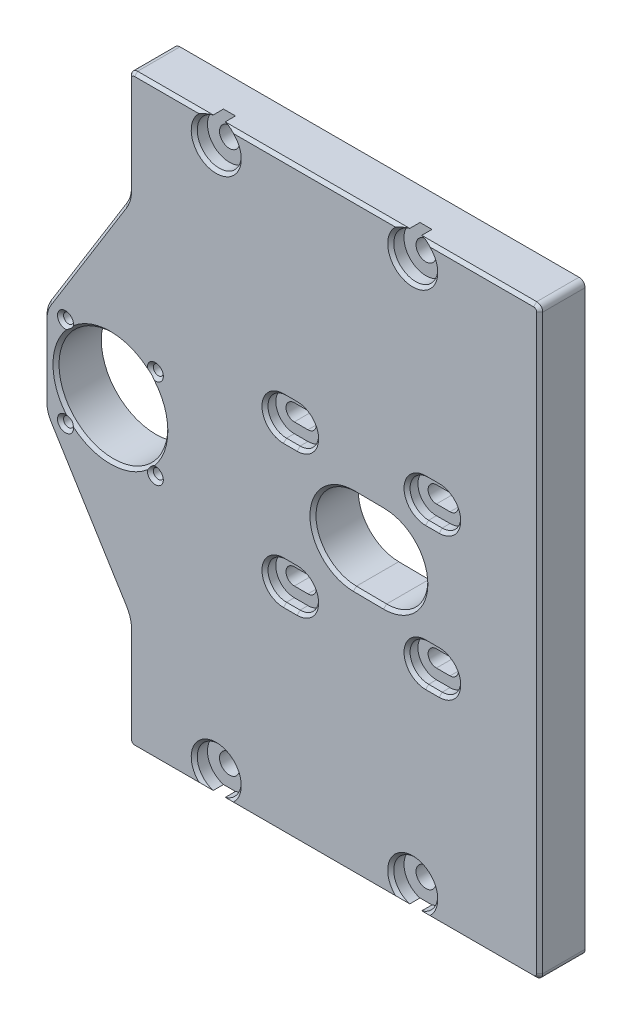
SolidWorks part; units mm, degrees
ref_plane "Front Plane" through (0, 0, 0) normal (0, 0, 1) x (1, 0, 0)
ref_plane "Top Plane" through (0, 0, 0) normal (0, 1, 0) x (1, 0, 0)
ref_plane "Right Plane" through (0, 0, 0) normal (1, 0, 0) x (0, 0, -1)
sketch "Sketch1" plane through (0, 0, 0) normal (0, 0, 1) x (1, 0, 0)
  line L24 (-148, 255) -> (-148, 190) construction
  line L31 (-148, 70) -> (-148, 10) construction
  line L32 (-148, 33.5) -> (-12, 33.5) construction
  line L36 (-12, 227) -> (-148, 227) construction
  line L37 (-148, 227) -> (-148, 190)
  line L38 (-148, 70) -> (-148, 33.5)
  line L39 (-148, 33.5) -> (-12, 33.5)
  line L43 (-12, 227) -> (-148, 227)
  line L45 (-176, 115.2267) -> (-176, 144.7733)
  line L46 (-176, 144.7733) -> (-148, 190)
  line L47 (-176, 115.2267) -> (-148, 70)
  line L51 (-12, 33.5) -> (-12, 227)
  circle A8 centre (-154, 130) radius 18
  circle A10 centre (-154, 130) radius 18
  dimension "D1" = 1
extrude "Boss-Extrude1" add sketch "Sketch1" along normal blind 15
sketch "Sketch2" plane through (0, 0, 15) normal (0, 0, 1) x (1, 0, 0)
  circle A1 centre (-139.1508, 115.1508) radius 2.25
  circle A3 centre (-168.8492, 115.1508) radius 2.25
  circle A5 centre (-168.8492, 144.8492) radius 2.25
  circle A7 centre (-139.1508, 144.8492) radius 2.25
hole_wizard "M4x0.7 Tapped Hole1" positions "Sketch3" profile "Sketch4" tap size "M4x0.7" standard "ANSI Metric"
sketch "Sketch3" plane through (0, 0, 15) normal (0, 0, 1) x (1, 0, 0)
  point P0 (-168.8492, 144.8492)
  point P3 (-139.1508, 144.8492)
  point P6 (-139.1508, 115.1508)
  point P9 (-168.8492, 115.1508)
sketch "Sketch4" plane through (-168.8492, 144.8492, 15) normal (1, 0, 0) x (0, -1, 0)
  line L0 (0, 0) -> (0, 20)
  line L1 (0, 20) -> (1.65, 19.0086)
  line L2 (1.65, 19.0086) -> (1.65, 0)
  line L5 (1.65, 0) -> (0, 0)
  line L10 (0, 20) -> (-1.65, 19.0086) construction
  line L11 (0, -6.35) -> (0, 107.95) construction
  dimension "Tap Drill Dia." = 3.3
  dimension "Tap Drill Depth" = 20
  dimension "Drill Angle" = 118
cosmetic thread "Hole Thread1" parameters "D1"=12, "D2"=4
cosmetic thread "Hole Thread2" parameters "D1"=12, "D2"=4
cosmetic thread "Hole Thread3" parameters "D1"=12, "D2"=4
cosmetic thread "Hole Thread4" parameters "D1"=12, "D2"=4
hole_wizard "CBORE for M6 Hex Head Bolt1" positions "Sketch5" profile "Sketch6" counterbore size "M6" standard "ANSI Metric"
sketch "Sketch5" plane through (0, 0, 15) normal (0, 0, 1) x (1, 0, 0)
  point P0 (-54, 220)
  point P3 (-119, 220)
  point P6 (-54, 40.5)
  point P9 (-119, 40.5)
sketch "Sketch6" plane through (-54, 220, 15) normal (1, 0, 0) x (0, -1, 0)
  line L0 (0, 0) -> (0, 29.9828)
  line L1 (0, 29.9828) -> (3.3, 28)
  line L2 (3.3, 28) -> (3.3, 4.38)
  line L3 (3.3, 4.38) -> (7.275, 4.38)
  line L4 (7.275, 4.38) -> (7.275, 0)
  line L5 (7.275, 0) -> (0, 0)
  line L10 (0, 29.9828) -> (-3.3, 28) construction
  line L11 (0, -6.35) -> (0, 107.95) construction
  dimension "Hole Dia." = 6.6
  dimension "Hole Depth" = 28
  dimension "C'Bore Dia." = 14.55
  dimension "C'Bore Depth" = 4.38
  dimension "Drill Angle" = 118
sketch "Sketch7" plane through (0, 0, 15) normal (0, 0, 1) x (1, 0, 0)
  line L0 (-73.5, 129.1439) -> (-88.5, 129.1439)
  line L1 (-89.5, 152.6439) -> (-94.5, 152.6439)
  line L2 (-42.5, 152.6439) -> (-47.5, 152.6439)
  line L3 (-42.5, 105.6439) -> (-47.5, 105.6439)
  line L4 (-89.5, 105.6439) -> (-94.5, 105.6439)
  circle A1 centre (-50, 105.6439) radius 2.85 construction
  circle A2 centre (-73.5, 129.1439) radius 13.5
  circle A3 centre (-73.5, 129.1439) radius 13.5
  circle A4 centre (-97, 105.6439) radius 2.85 construction
  circle A5 centre (-97, 152.6439) radius 2.85 construction
  circle A6 centre (-50, 152.6439) radius 2.85 construction
  circle A7 centre (-50, 105.6439) radius 2.85
  circle A8 centre (-97, 105.6439) radius 2.85
  circle A9 centre (-97, 152.6439) radius 2.85
  circle A10 centre (-50, 152.6439) radius 2.85
  dimension "D1" = 1
hole_wizard "Ø1.0mm Dowel Slot1" positions "Sketch8" profile "Sketch9" size "Ø1.0" standard "ANSI Metric" slot yes
sketch "Sketch8" plane through (0, 0, 15) normal (0, 0, 1) x (1, 0, 0)
  line L0 (-86.9991, 129.3233) -> (-50.0009, 128.9645) construction
  point P0 (-68.5, 129.1439)
  dimension "D1" = 37
sketch "Sketch9" plane through (-68.5, 129.1439, 15) normal (1, 0, 0) x (0, -1, 0)
  line L0 (0, 0) -> (0, 36.1116)
  line L1 (0, 36.1116) -> (13.5, 28)
  line L2 (13.5, 28) -> (13.5, 0)
  line L5 (13.5, 0) -> (0, 0)
  line L10 (0, 36.1116) -> (-13.5, 28) construction
  line L11 (0, -6.35) -> (0, 107.95) construction
  dimension "Hole Dia." = 27
  dimension "Hole Depth" = 28
  dimension "Drill Angle" = 118
hole_wizard "CBORE SLOT for M5 Hex Head Bolt1" positions "Sketch10" profile "Sketch11" size "M5" standard "ANSI Metric" slot yes
sketch "Sketch10" plane through (0, 0, 15) normal (0, 0, 1) x (1, 0, 0)
  line L0 (-99.5, 152.6439) -> (-89.5, 152.6439) construction
  point P0 (-94.5, 152.6439)
  point P5 (-94.5, 105.6439)
  point P8 (-47.5, 152.6439)
  point P11 (-47.5, 105.6439)
  dimension "D1" = 10
sketch "Sketch11" plane through (-94.5, 152.6439, 15) normal (1, 0, 0) x (0, -1, 0)
  line L0 (0, 0) -> (0, 29.6524)
  line L1 (0, 29.6524) -> (2.75, 28)
  line L2 (2.75, 28) -> (2.75, 3.58)
  line L3 (2.75, 3.58) -> (6.12, 3.58)
  line L4 (6.12, 3.58) -> (6.12, 0)
  line L5 (6.12, 0) -> (0, 0)
  line L10 (0, 29.6524) -> (-2.75, 28) construction
  line L11 (0, -6.35) -> (0, 107.95) construction
  dimension "Hole Dia." = 5.5
  dimension "Hole Depth" = 28
  dimension "C'Bore Dia." = 12.24
  dimension "C'Bore Depth" = 3.58
  dimension "Drill Angle" = 118
fillet "Fillet1" radius 10 4 edges at (-148, 70, 7.5) (-176, 115.2267, 7.5) (-176, 144.7733, 7.5) (-148, 190, 7.5)
fillet "Fillet2" radius 2 4 edges at (-148, 33.5, 7.5) (-12, 33.5, 7.5) (-12, 227, 7.5) (-148, 227, 7.5)
chamfer "Chamfer1" distance 1 angle 45 49 edges at (-148.3817, 69.8914, 15) (-162, 92.6134, 15) (-175.6183, 115.3353, 15) (-176, 130, 15) (-175.6183, 144.6647, 15) (-162, 167.3866, 15) (-148.3817, 190.1086, 15) (-148, 208.9225, 15) (-147.4142, 226.4142, 15) (-133.4907, 227, 15) (-119, 212.725, 15) (-86.5, 227, 15) (-54, 212.725, 15) (-33.0093, 227, 15) (-12.5858, 226.4142, 15) (-12, 130.25, 15) (-12.5858, 34.0858, 15) (-33.0093, 33.5, 15) (-54, 47.775, 15) (-86.5, 33.5, 15) (-119, 47.775, 15) (-133.4907, 33.5, 15) (-147.4142, 34.0858, 15) (-148, 51.3275, 15) (-167.1992, 115.1508, 15) (-137.5008, 115.1508, 15) (-137.5008, 144.8492, 15) (-167.1992, 144.8492, 15) (-86.9991, 129.3233, 15) (-68.6309, 115.6445, 15) (-50.0009, 128.9645, 15) (-68.3691, 142.6433, 15) (-55.87, 105.6439, 15) (-47.5, 99.5239, 15) (-39.13, 105.6439, 15) (-47.5, 111.7639, 15) (-47.5, 146.5239, 15) (-39.13, 152.6439, 15) (-47.5, 158.7639, 15) (-55.87, 152.6439, 15) (-94.5, 99.5239, 15) (-86.13, 105.6439, 15) (-94.5, 111.7639, 15) (-102.87, 105.6439, 15) (-102.87, 152.6439, 15) (-94.5, 146.5239, 15) (-86.13, 152.6439, 15) (-94.5, 158.7639, 15) (-136, 130, 15)
